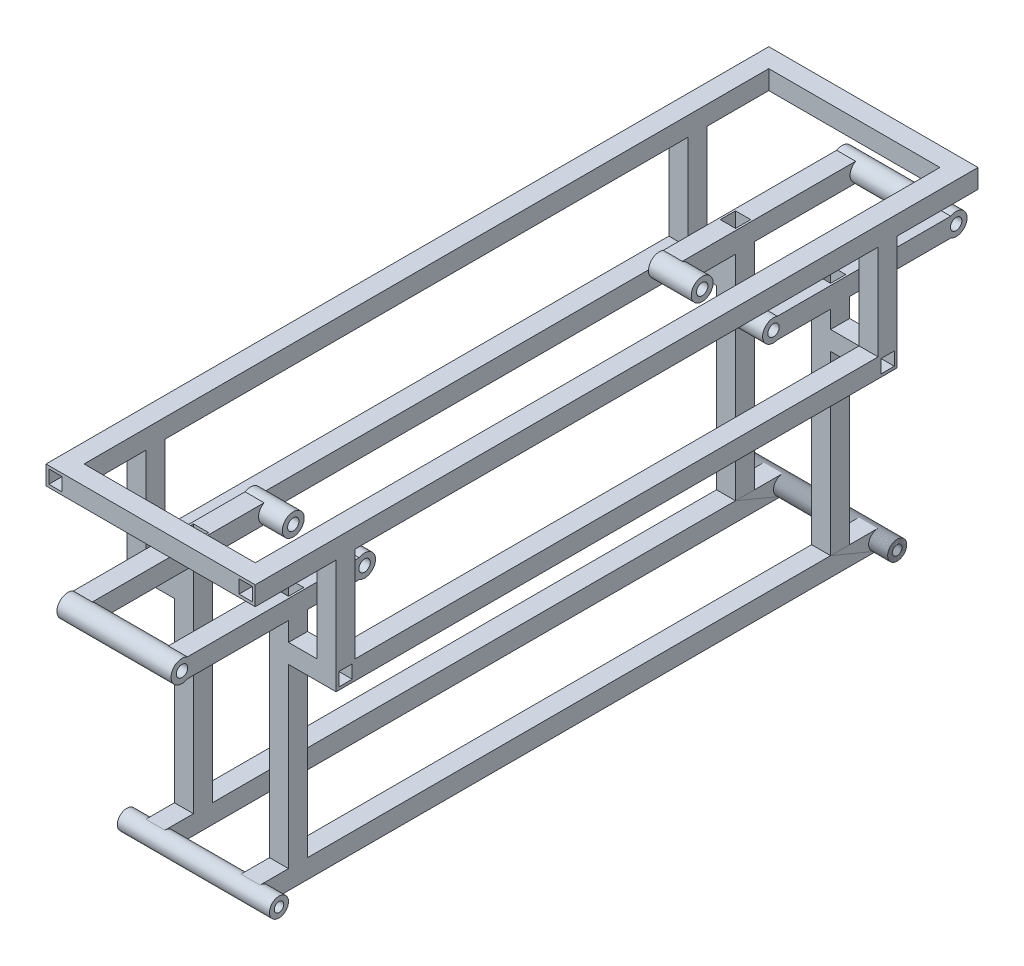
SolidWorks part; units mm, degrees
ref_plane "Płaszczyzna przednia" through (0, 0, 0) normal (0, 0, 1) x (1, 0, 0)
ref_plane "Płaszczyzna górna" through (0, 0, 0) normal (0, 1, 0) x (1, 0, 0)
ref_plane "Płaszczyzna prawa" through (0, 0, 0) normal (1, 0, 0) x (0, 0, -1)
sketch "Szkic1" plane through (0, 0, 0) normal (1, 0, 0) x (0, 0, -1)
  circle A0 centre (0, 0) radius 5
  circle A1 centre (0, 0) radius 10
  dimension "D1" = 10
  dimension "D2" = 20
extrude "Dodanie-wyciągnięcie1" add sketch "Szkic1" along normal mid plane 160
ref_plane "Płaszczyzna1" through (0, 0, 325) normal (0, 0, 1) x (1, 0, 0)
ref_plane "Płaszczyzna2" through (0, 0, 650) normal (0, 0, 1) x (1, 0, 0)
sketch "Szkic2" plane through (0, 0, 0) normal (1, 0, 0) x (0, 0, -1)
  line L0 (0, 0) -> (-650, 0)
  line L1 (-650, 11) -> (-650, -11) construction
  line L2 (11, 0) -> (-11, 0) construction
  circle A0 centre (-650, 0) radius 5
  circle A1 centre (-650, 0) radius 10
  dimension "D1" = 10
  dimension "D2" = 20
extrude "Dodanie-wyciągnięcie2" add sketch "Szkic2" along normal mid plane 160 separate body contours A1 A0 region at (0, 0, 659.7172)
sketch "Szkic3" plane through (0, 0, 325) normal (0, 0, 1) x (1, 0, 0)
  line L0 (88, 0) -> (-88, 0) construction
  line L1 (40, -10) -> (60, -10)
  line L2 (40, -10) -> (40, 10)
  line L3 (40, 10) -> (60, 10)
  line L4 (60, -10) -> (60, 10)
  line L5 (40, -10) -> (60, 10) construction
  line L6 (40, 10) -> (60, -10) construction
  line L7 (80, 10) -> (-80, 10) construction
  line L8 (80, -10) -> (80, 10) construction
  line L9 (-60, -10) -> (-40, -10)
  line L10 (-60, -10) -> (-60, 10)
  line L11 (-60, 10) -> (-40, 10)
  line L12 (-40, -10) -> (-40, 10)
  line L13 (-60, -10) -> (-40, 10) construction
  line L14 (-60, 10) -> (-40, -10) construction
  line L15 (-42, -8) -> (-42, 8)
  line L16 (-58, 8) -> (-42, 8)
  line L17 (-58, -8) -> (-58, 8)
  line L18 (-58, -8) -> (-42, -8)
  line L19 (58, -8) -> (58, 8)
  line L20 (42, 8) -> (58, 8)
  line L21 (42, -8) -> (42, 8)
  line L22 (42, -8) -> (58, -8)
  point P0 (50, 0)
  point P9 (-50, 0)
  dimension "D1" = 20
  dimension "D2" = 20
  dimension "D3" = 20
  dimension "D4" = 20
  dimension "D5" = 2
extrude "Dodanie-wyciągnięcie3" add sketch "Szkic3" along normal up to next
mirror "Lustro3" about plane through (0, 0, 325) normal (0, 0, 1) of bodies 105
sketch "Szkic4" plane through (0, 10, 0) normal (0, 1, 0) x (1, 0, 0)
  line L0 (40, -650) -> (40, -325) construction
  line L1 (40, -620) -> (60, -620)
  line L2 (40, -620) -> (40, -600)
  line L3 (40, -600) -> (60, -600)
  line L4 (60, -620) -> (60, -600)
  line L5 (60, -650) -> (60, -325) construction
  line L6 (-60, -650) -> (-60, -325) construction
  line L7 (-60, -620) -> (-40, -620)
  line L8 (-60, -620) -> (-60, -600)
  line L9 (-60, -600) -> (-40, -600)
  line L10 (-40, -620) -> (-40, -600)
  line L11 (-40, -650) -> (-40, -325) construction
  line L12 (-11, -650) -> (11, -650) construction
  line L13 (-42, -618) -> (-42, -602)
  line L14 (-58, -602) -> (-42, -602)
  line L15 (-58, -618) -> (-58, -602)
  line L16 (-58, -618) -> (-42, -618)
  line L17 (58, -618) -> (58, -602)
  line L18 (42, -602) -> (58, -602)
  line L19 (42, -618) -> (42, -602)
  line L20 (42, -618) -> (58, -618)
  dimension "D1" = 20
  dimension "D2" = 20
  dimension "D3" = 30
  dimension "D4" = 30
  dimension "D5" = 2
extrude "Dodanie-wyciągnięcie4" add sketch "Szkic4" along normal blind 246
mirror "Lustro4" about plane through (0, 0, 325) normal (0, 0, 1) of bodies 107
sketch "Szkic5" plane through (0, 0, 620) normal (0, 0, 1) x (1, 0, 0)
  line L0 (-40, 256) -> (-40, 10) construction
  line L1 (-60, 256) -> (-40, 256)
  line L2 (-60, 256) -> (-60, 236)
  line L3 (-60, 236) -> (-40, 236)
  line L4 (-40, 256) -> (-40, 236)
  line L5 (60, 256) -> (60, 10) construction
  line L6 (40, 256) -> (60, 256)
  line L7 (40, 256) -> (40, 236)
  line L8 (40, 236) -> (60, 236)
  line L9 (60, 256) -> (60, 236)
  line L10 (-57, 239) -> (-43, 239)
  line L11 (-43, 253) -> (-43, 239)
  line L12 (-57, 253) -> (-43, 253)
  line L13 (-57, 253) -> (-57, 239)
  line L14 (43, 239) -> (57, 239)
  line L15 (57, 253) -> (57, 239)
  line L16 (43, 253) -> (57, 253)
  line L17 (43, 253) -> (43, 239)
  dimension "D1" = 20
  dimension "D2" = 20
  dimension "D3" = 3
extrude "Dodanie-wyciągnięcie5" add sketch "Szkic5" along normal blind 112
sketch "Szkic6" plane through (60, 0, 0) normal (1, 0, 0) x (0, 0, -1)
  line L0 (-732, 236) -> (-732, 256) construction
  circle A0 centre (-732, 246) radius 11.5
  dimension "D1" = 23
extrude "Dodanie-wyciągnięcie6" add sketch "Szkic6" against normal blind 120
sketch "Szkic7" plane through (60, 0, 0) normal (1, 0, 0) x (0, 0, -1)
  circle A0 centre (-732, 246) radius 6
  dimension "D1" = 12
extrude "Wytnij-wyciągnięcie1" cut sketch "Szkic7" against normal blind 120
sketch "Szkic8" plane through (0, 0, 30) normal (0, 0, -1) x (-1, 0, 0)
  line L0 (-40, 236) -> (-40, 256) construction
  line L1 (-60, 256) -> (-40, 256)
  line L2 (-60, 256) -> (-60, 236)
  line L3 (-60, 236) -> (-40, 236)
  line L4 (-40, 256) -> (-40, 236)
  line L5 (-57, 239) -> (-43, 239)
  line L6 (40, 256) -> (60, 256)
  line L7 (40, 256) -> (40, 236)
  line L8 (40, 236) -> (60, 236)
  line L9 (60, 256) -> (60, 236)
  line L10 (-43, 253) -> (-43, 239)
  line L11 (-57, 253) -> (-43, 253)
  line L12 (-57, 253) -> (-57, 239)
  line L13 (43, 239) -> (57, 239)
  line L14 (57, 253) -> (57, 239)
  line L15 (43, 253) -> (57, 253)
  line L16 (43, 253) -> (43, 239)
  dimension "D1" = 20
  dimension "D2" = 3
extrude "Dodanie-wyciągnięcie7" add sketch "Szkic8" along normal blind 112
sketch "Szkic9" plane through (-60, 0, 0) normal (-1, 0, 0) x (0, 0, 1)
  line L0 (-82, 236) -> (-82, 256) construction
  circle A0 centre (-82, 246) radius 11.5
  dimension "D1" = 23
extrude "Dodanie-wyciągnięcie8" add sketch "Szkic9" against normal blind 120
sketch "Szkic10" plane through (-60, 0, 0) normal (-1, 0, 0) x (0, 0, 1)
  circle A0 centre (-82, 246) radius 6
  dimension "D1" = 12
extrude "Wytnij-wyciągnięcie2" cut sketch "Szkic10" against normal blind 120
sketch "Szkic11" plane through (0, 0, 50) normal (0, 0, 1) x (1, 0, 0)
  line L0 (-40, 236) -> (-40, 10) construction
  line L1 (-60, 256) -> (-40, 256)
  line L2 (-60, 256) -> (-60, 234.5)
  line L3 (-60, 234.5) -> (-40, 234.5)
  line L4 (-40, 256) -> (-40, 234.5)
  line L5 (-60, 234.5) -> (60, 234.5) construction
  line L6 (57, 253) -> (43, 253)
  line L7 (60, 234.5) -> (40, 234.5)
  line L8 (60, 234.5) -> (60, 256)
  line L9 (60, 256) -> (40, 256)
  line L10 (40, 234.5) -> (40, 256)
  line L11 (43, 237.5) -> (43, 253)
  line L12 (57, 237.5) -> (43, 237.5)
  line L13 (57, 237.5) -> (57, 253)
  line L14 (-43, 253) -> (-43, 237.5)
  line L15 (-57, 237.5) -> (-43, 237.5)
  line L16 (-57, 253) -> (-57, 237.5)
  line L17 (-57, 253) -> (-43, 253)
  dimension "D1" = 20
  dimension "D2" = 3
extrude "Dodanie-wyciągnięcie9" add sketch "Szkic11" along normal blind 60
sketch "Szkic12" plane through (-60, 0, 0) normal (-1, 0, 0) x (0, 0, 1)
  line L0 (110, 256) -> (110, 234.5) construction
  circle A0 centre (110, 245.25) radius 11.5
  dimension "D1" = 23
extrude "Dodanie-wyciągnięcie10" add sketch "Szkic12" against normal blind 120
sketch "Szkic13" plane through (0, 256, 0) normal (0, 1, 0) x (1, 0, 0)
  line L1 (15, -81.6584) -> (-15, -81.6584)
  line L2 (15, -81.6584) -> (15, -141.6584)
  line L3 (15, -141.6584) -> (-15, -141.6584)
  line L4 (-15, -81.6584) -> (-15, -141.6584)
  line L5 (-40, 76.3211) -> (-40, -105.915) construction
  dimension "D1" = 30
  dimension "D2" = 60
  dimension "D3" = 25
extrude "Wytnij-wyciągnięcie3" cut sketch "Szkic13" against normal mid plane 120
sketch "Szkic14" plane through (-60, 0, 0) normal (-1, 0, 0) x (0, 0, 1)
  circle A0 centre (110, 245.25) radius 6
  dimension "D1" = 12
extrude "Wytnij-wyciągnięcie4" cut sketch "Szkic14" against normal blind 120
sketch "Szkic15" plane through (0, 0, 600) normal (0, 0, -1) x (-1, 0, 0)
  line L6 (-40, 256) -> (-40, 10) construction
  line L7 (-60, 256) -> (-40, 256)
  line L8 (-60, 256) -> (-60, 236)
  line L9 (-60, 236) -> (-40, 236)
  line L10 (-40, 256) -> (-40, 236)
  line L11 (40, 256) -> (40, 10) construction
  line L12 (60, 256) -> (40, 256)
  line L13 (60, 256) -> (60, 236)
  line L14 (60, 236) -> (40, 236)
  line L15 (40, 256) -> (40, 236)
  line L16 (57, 253) -> (57, 239)
  line L17 (57, 239) -> (43, 239)
  line L18 (43, 253) -> (43, 239)
  line L19 (57, 253) -> (43, 253)
  line L20 (-43, 253) -> (-43, 239)
  line L21 (-57, 239) -> (-43, 239)
  line L22 (-57, 253) -> (-57, 239)
  line L23 (-57, 253) -> (-43, 253)
  dimension "D1" = 20
  dimension "D2" = 20
  dimension "D3" = 3
extrude "Dodanie-wyciągnięcie11" add sketch "Szkic15" along normal blind 60
sketch "Szkic16" plane through (60, 0, 0) normal (1, 0, 0) x (0, 0, -1)
  line L0 (-540, 256) -> (-540, 236) construction
  circle A0 centre (-540, 246) radius 11.5
  dimension "D1" = 23
extrude "Dodanie-wyciągnięcie12" add sketch "Szkic16" against normal blind 120
sketch "Szkic17" plane through (60, 0, 0) normal (1, 0, 0) x (0, 0, -1)
  circle A0 centre (-540, 246) radius 6
  dimension "D1" = 12
extrude "Wytnij-wyciągnięcie5" cut sketch "Szkic17" against normal blind 120
sketch "Szkic18" plane through (0, 256, 0) normal (0, 1, 0) x (1, 0, 0)
  line L0 (0, -17.4508) -> (0, 17.4508) construction
  line L1 (15, -518.0896) -> (-15, -518.0896)
  line L2 (15, -518.0896) -> (15, -558.0896)
  line L3 (15, -558.0896) -> (-15, -558.0896)
  line L4 (-15, -518.0896) -> (-15, -558.0896)
  line L5 (15, -518.0896) -> (-15, -558.0896) construction
  line L6 (15, -558.0896) -> (-15, -518.0896) construction
  point P0 (0, -538.0896)
  dimension "D1" = 30
  dimension "D2" = 40
extrude "Wytnij-wyciągnięcie6" cut sketch "Szkic18" against normal mid plane 120
sketch "Szkic19" plane through (60, 0, 0) normal (1, 0, 0) x (0, 0, -1)
  line L0 (-620, 236) -> (-620, 10) construction
  line L1 (-620, 216) -> (-600, 216)
  line L2 (-620, 216) -> (-620, 196)
  line L3 (-620, 196) -> (-600, 196)
  line L4 (-600, 216) -> (-600, 196)
  line L5 (-600, 236) -> (-600, 10) construction
  line L6 (-726.3211, 256) -> (-545.6789, 256) construction
  line L7 (-617, 213) -> (-603, 213)
  line L8 (-603, 213) -> (-603, 199)
  line L9 (-617, 199) -> (-603, 199)
  line L10 (-617, 213) -> (-617, 199)
  dimension "D1" = 20
  dimension "D2" = 40
  dimension "D3" = 3
extrude "Dodanie-wyciągnięcie13" add sketch "Szkic19" along normal blind 50
mirror "Lustro5" about plane through (0, 0, 0) normal (1, 0, 0) of "Dodanie-wyciągnięcie13"
sketch "Szkic20" plane through (60, 0, 0) normal (1, 0, 0) x (0, 0, -1)
  line L0 (-50, 234.5) -> (-50, 10) construction
  line L1 (-50, 216) -> (-30, 216)
  line L2 (-50, 216) -> (-50, 196)
  line L3 (-50, 196) -> (-30, 196)
  line L4 (-30, 216) -> (-30, 196)
  line L5 (-30, 236) -> (-30, 10) construction
  line L6 (76.3211, 256) -> (-105.915, 256) construction
  line L7 (-33, 213) -> (-33, 199)
  line L8 (-47, 199) -> (-33, 199)
  line L9 (-47, 213) -> (-47, 199)
  line L10 (-47, 213) -> (-33, 213)
  dimension "D1" = 20
  dimension "D2" = 40
  dimension "D3" = 3
extrude "Dodanie-wyciągnięcie14" add sketch "Szkic20" along normal blind 50
mirror "Lustro7" about plane through (0, 0, 0) normal (1, 0, 0) of "Dodanie-wyciągnięcie14"
sketch "Szkic21" plane through (0, 216, 0) normal (0, 1, 0) x (1, 0, 0)
  line L0 (110, -620) -> (60, -620) construction
  line L1 (110, -600) -> (90, -600)
  line L2 (110, -600) -> (110, -620)
  line L3 (110, -620) -> (90, -620)
  line L4 (90, -600) -> (90, -620)
  line L5 (107, -603) -> (93, -603)
  line L6 (93, -603) -> (93, -617)
  line L7 (107, -617) -> (93, -617)
  line L8 (107, -603) -> (107, -617)
  dimension "D1" = 20
  dimension "D2" = 3
extrude "Dodanie-wyciągnięcie15" add sketch "Szkic21" along normal blind 100
mirror "Lustro8" about plane through (0, 0, 0) normal (1, 0, 0) of "Dodanie-wyciągnięcie15"
sketch "Szkic22" plane through (0, 216, 0) normal (0, 1, 0) x (1, 0, 0)
  line L0 (110, -50) -> (60, -50) construction
  line L1 (110, -30) -> (90, -30)
  line L2 (110, -30) -> (110, -50)
  line L3 (110, -50) -> (90, -50)
  line L4 (90, -30) -> (90, -50)
  line L5 (107, -33) -> (93, -33)
  line L6 (93, -33) -> (93, -47)
  line L7 (107, -47) -> (93, -47)
  line L8 (107, -33) -> (107, -47)
  dimension "D1" = 20
  dimension "D2" = 3
extrude "Dodanie-wyciągnięcie16" add sketch "Szkic22" along normal blind 100
mirror "Lustro9" about plane through (0, 0, 0) normal (1, 0, 0) of "Dodanie-wyciągnięcie16"
sketch "Szkic23" plane through (0, 0, 620) normal (0, 0, 1) x (1, 0, 0)
  line L0 (93, 333) -> (107, 333)
  line L1 (90, 316) -> (110, 316)
  line L2 (90, 316) -> (90, 336)
  line L3 (90, 336) -> (110, 336)
  line L4 (110, 316) -> (110, 336)
  line L5 (107, 319) -> (107, 333)
  line L6 (93, 319) -> (107, 319)
  line L7 (93, 319) -> (93, 333)
  dimension "D1" = 20
  dimension "D2" = 20
  dimension "D3" = 3
extrude "Dodanie-wyciągnięcie17" add sketch "Szkic23" against normal blind 675
sketch "Szkic24" plane through (0, 0, 620) normal (0, 0, 1) x (1, 0, 0)
  line L0 (90, 336) -> (90, 216) construction
  line L1 (110, 336) -> (90, 336)
  line L2 (110, 336) -> (110, 316)
  line L3 (110, 316) -> (90, 316)
  line L4 (90, 336) -> (90, 316)
  line L5 (93, 333) -> (93, 319) construction
  line L6 (107, 333) -> (93, 333)
  line L7 (107, 333) -> (107, 319)
  line L8 (107, 319) -> (93, 319)
  line L9 (93, 333) -> (93, 319)
  dimension "D1" = 20
extrude "Dodanie-wyciągnięcie18" add sketch "Szkic24" along normal blind 85
mirror "Lustro10" about plane through (0, 0, 0) normal (1, 0, 0) of "Dodanie-wyciągnięcie17", "Dodanie-wyciągnięcie18"
sketch "Szkic25" plane through (-90, 0, 0) normal (1, 0, 0) x (0, 0, -1)
  line L0 (-705, 316) -> (-620, 316) construction
  line L1 (-705, 336) -> (-685, 336)
  line L2 (-705, 336) -> (-705, 316)
  line L3 (-705, 316) -> (-685, 316)
  line L4 (-685, 336) -> (-685, 316)
  line L5 (-702, 333) -> (-688, 333)
  line L6 (-688, 333) -> (-688, 319)
  line L7 (-702, 319) -> (-688, 319)
  line L8 (-702, 333) -> (-702, 319)
  dimension "D1" = 20
  dimension "D2" = 3
extrude "Dodanie-wyciągnięcie19" add sketch "Szkic25" along normal up to next
mirror "Lustro12" about plane through (0, 0, 325) normal (0, 0, 1) of "Dodanie-wyciągnięcie19"
sketch "Szkic26" plane through (0, 0, 50) normal (0, 0, 1) x (1, 0, 0)
  line L0 (107, 213) -> (93, 213)
  line L1 (110, 196) -> (90, 196)
  line L2 (110, 196) -> (110, 216)
  line L3 (110, 216) -> (90, 216)
  line L4 (90, 196) -> (90, 216)
  line L5 (93, 199) -> (93, 213)
  line L6 (107, 199) -> (93, 199)
  line L7 (107, 199) -> (107, 213)
  dimension "D1" = 3
extrude "Dodanie-wyciągnięcie20" add sketch "Szkic26" along normal up to next (550 mm away)
mirror "Lustro13" about plane through (0, 0, 0) normal (1, 0, 0) of "Dodanie-wyciągnięcie20"
